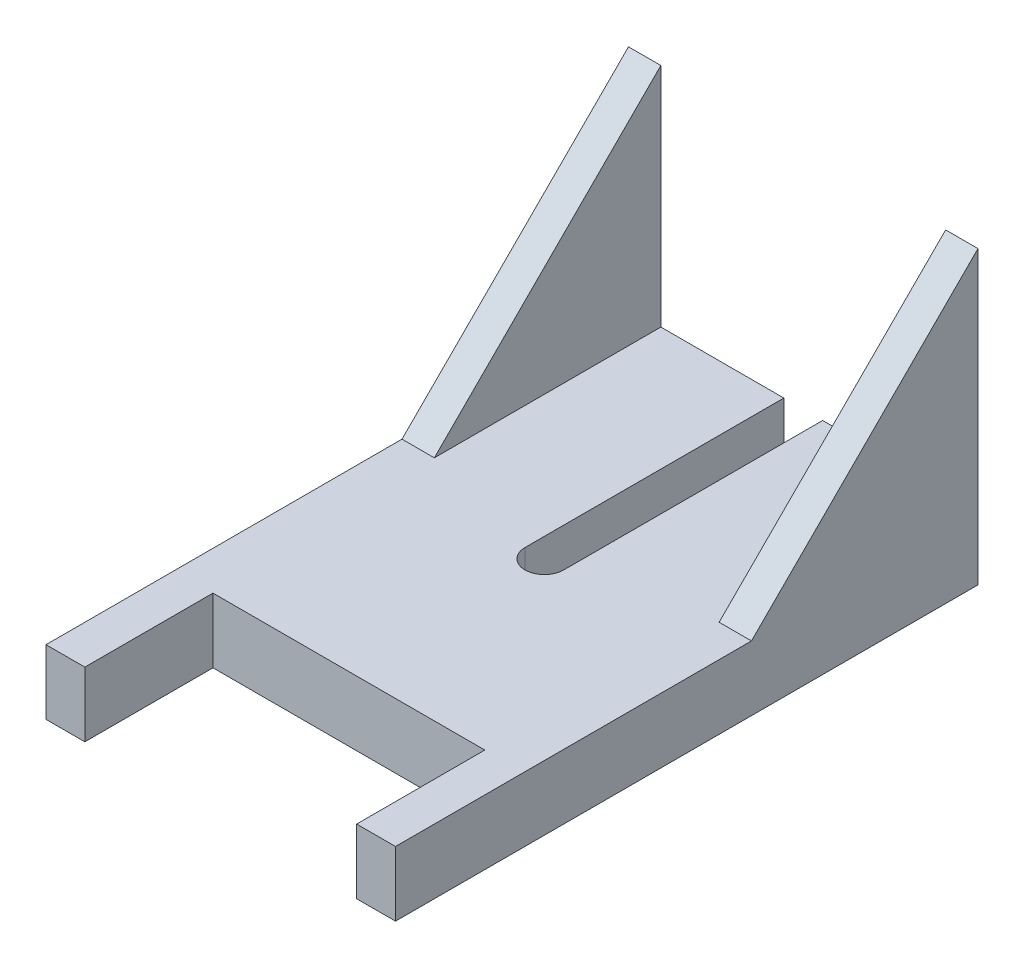
SolidWorks part; units mm, degrees
ref_plane "Front Plane" through (0, 0, 0) normal (0, 0, 1) x (1, 0, 0)
ref_plane "Top Plane" through (0, 0, 0) normal (0, 1, 0) x (1, 0, 0)
ref_plane "Right Plane" through (0, 0, 0) normal (1, 0, 0) x (0, 0, -1)
sketch "Sketch1" plane through (0, 0, 0) normal (0, 0, 1) x (1, 0, 0)
  line L0 (-16.0284, 532.1756) -> (37.9716, 532.1756)
  line L1 (-16.0284, 532.1756) -> (-16.0284, 522.1756)
  line L2 (-16.0284, 522.1756) -> (37.9716, 522.1756)
  line L3 (37.9716, 532.1756) -> (37.9716, 522.1756)
  dimension "D1" = 54
  dimension "D2" = 10
extrude "Boss-Extrude1" add sketch "Sketch1" along normal blind 90 contours L0 L3 L2 L1
sketch "Sketch2" plane through (0, 522.1756, 0) normal (0, -1, 0) x (1, 0, 0)
  line L0 (-16.0284, 90) -> (37.9716, 90) construction
  line L1 (-10.0284, 90) -> (31.9716, 90)
  line L2 (-10.0284, 90) -> (-10.0284, 70.2)
  line L3 (-10.0284, 70.2) -> (31.9716, 70.2)
  line L4 (31.9716, 90) -> (31.9716, 70.2)
  line L6 (-16.0284, 90) -> (-16.0284, 0) construction
  dimension "D1" = 42
  dimension "D2" = 19.8
  dimension "D3" = 6
extrude "Cut-Extrude1" cut sketch "Sketch2" against normal through all
sketch "Sketch4" plane through (0, 532.1756, 0) normal (0, 1, 0) x (1, 0, 0)
  line L0 (10.9716, -70.2) -> (10.9716, 0) construction
  line L1 (-10.0284, -70.2) -> (31.9716, -70.2) construction
  line L2 (-16.0284, 0) -> (37.9716, 0) construction
  line L3 (10.9716, -40) -> (10.9716, 0) construction
  line L4 (7.9716, -40) -> (7.9716, 0)
  line L5 (13.9716, -40) -> (13.9716, 0)
  arc A0 (7.9716, -40) -> (13.9716, -40) centre (10.9716, -40) ccw
  arc A1 (13.9716, 0) -> (7.9716, 0) centre (10.9716, 0) ccw
  point P7 (10.9716, -20)
extrude "Cut-Extrude2" cut sketch "Sketch4" against normal through all
sketch "Sketch7" plane through (-16.0284, 0, 0) normal (-1, 0, 0) x (0, 0, 1)
  line L0 (35, 532.1756) -> (0, 567.1756)
  line L1 (90, 532.1756) -> (0, 532.1756) construction
  line L2 (0, 654.6756) -> (0, 354.6756) construction
  line L3 (0, 567.1756) -> (0, 532.1756)
  line L4 (0, 532.1756) -> (35, 532.1756)
  point P6 (30.9623, 532.1756)
extrude "Boss-Extrude4" add sketch "Sketch7" against normal blind 5
sketch "Sketch8" plane through (37.9716, 0, 0) normal (1, 0, 0) x (0, 0, -1)
  line L0 (-35, 532.1756) -> (0, 567.1756)
  line L1 (0, 567.1756) -> (0, 532.1756)
  line L2 (0, 532.1756) -> (-35, 532.1756)
extrude "Boss-Extrude5" add sketch "Sketch8" against normal blind 5
